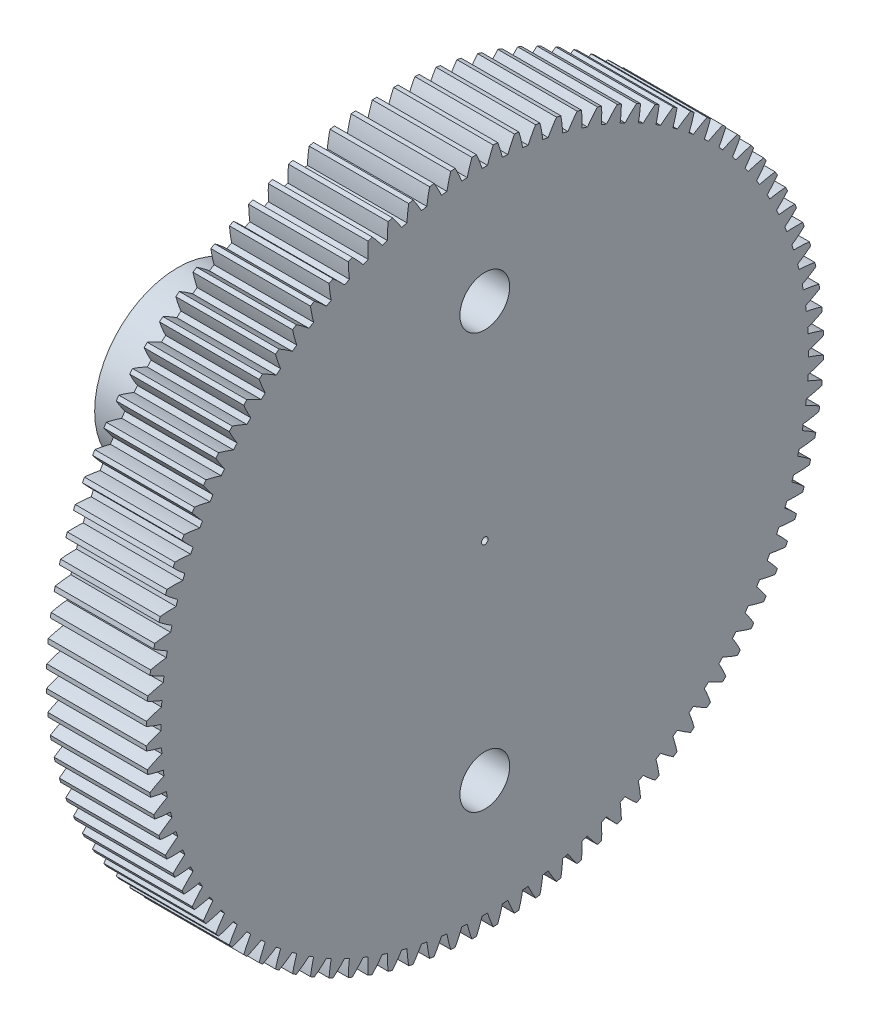
SolidWorks part; units mm, degrees
ref_plane "Plane1" through (0, 0, 0) normal (0, 0, 1) x (1, 0, 0)
ref_plane "Plane2" through (0, 0, 0) normal (0, 1, 0) x (1, 0, 0)
ref_plane "Plane3" through (0, 0, 0) normal (1, 0, 0) x (0, 0, -1)
other "Configuration Table"
sketch "HoldingSke" plane through (0, 0, 0) normal (0, 1, 0) x (1, 0, 0)
  line L0 (0, 0) -> (-0.2171, -1.231)
  line L1 (-15, 0) -> (100, 0) construction
  line L2 (0, 0) -> (-2.1039, 2.3779)
  line L3 (0, 0) -> (-11.863, 4.5341)
  line L4 (0, 0) -> (-1.4996, 8.5048)
  line L5 (0, 0) -> (-46.8476, -17.4728)
  line L6 (0, 0) -> (-9.9476, -6.7116)
  line L7 (-2.1039, 2.3779) -> (8.6586, 51.2059)
  line L8 (-76.2, 54.61) -> (-76.1, 54.61)
  line L9 (-71.009, 38.7566) -> (-53.1078, 45.2721)
  line L10 (-76.2, 71.12) -> (104.1128, 71.12)
  line L11 (0, 0) -> (-12, 0)
  line L12 (-76.2, 101.6) -> (-76.17, 101.6)
  line L13 (24.9733, 27.94) -> (52.9518, 28.4284)
  line L14 (24.9733, 27.94) -> (24.9743, 27.94)
  line L15 (24.9733, 27.94) -> (100.4006, 29.5858)
  line L16 (-63.627, -0.8) -> (-12.827, -0.8)
  circle A0 centre (0, 0) radius 0.4
  circle A1 centre (0, 0) radius 10
  circle A2 centre (0, 0) radius 10
  circle A3 centre (0, 0) radius 0.4
  dimension "Num_teeth" = 100
  dimension "Pitch_radius" = 180.3128
  dimension "Width" = 12
  dimension "Thickness" = 12
sketch "BasProSke" plane through (0, 0, 0) normal (0, 1, 0) x (1, 0, 0)
  line L0 (-10, 0) -> (60, 0) construction
  line L1 (0, 0) -> (0, 40.8)
  line L2 (0, 0) -> (12, 0)
  line L3 (12, 0) -> (12, 40.8)
  line L4 (12, 40.8) -> (0, 40.8)
  dimension "Thickness" = 12
  dimension "Diameter" = 81.6
revolve "Base-Revolve" add sketch "BasProSke" angle 360 about L0
sketch "TooCutSke" plane through (0, 0, 0) normal (1, 0, 0) x (0, 0, -1)
  line L1 (0, 0) -> (0, 107) construction
  line L2 (0, 0) -> (-0.6808, 39.9942) construction
  line L3 (0, 0) -> (-2.5126, 79.9522) construction
  line L4 (-0.6808, 39.9942) -> (-1.2563, 39.9761) construction
  arc A0 (0.331, 38.9976) -> (-0.331, 38.9976) centre (0, 0) ccw
  arc A1 (1.0251, 40.8125) -> (-1.0251, 40.8125) centre (0, 0) ccw
  circle A2 centre (0, 0) radius 40 construction
  circle A3 centre (0, 0) radius 37.5877 construction
  arc A4 (-0.331, 38.9976) -> (-1.0251, 40.8125) centre (-15.5948, 34.2) ccw
  arc A5 (1.0251, 40.8125) -> (0.331, 38.9976) centre (15.5948, 34.2) ccw
extrude "ToothCut" cut sketch "TooCutSke" along normal through all
fillet "Breaks" [suppressed] radius 0.016 tangent propagation no
fillet "RootFillets" [suppressed] radius 0.201
pattern_circular "TeethCuts" count 100 every 3.6 about axis through (-10, 0, 0) along (1, 0, 0) of "ToothCut", "RootFillets", "Breaks"
sketch "HubNeaOneSke" plane through (0, 0, 0) normal (-1, 0, 0) x (0, 0, 1)
  circle A0 centre (0, 0) radius 10
  dimension "Diameter" = 20
sketch "HubNeaBotSke" plane through (0, 0, 0) normal (-1, 0, 0) x (0, 0, 1)
  circle A0 centre (0, 0) radius 10
  dimension "Diameter" = 20
extrude "HubNearBoth" [suppressed] add sketch "HubNeaBotSke" along normal blind 19.0001
ref_plane "FarPln" through (12, 0, 0) normal (1, 0, 0) x (0, 0, -1)
sketch "HubFarSke" plane through (12, 0, 0) normal (1, 0, 0) x (0, 0, -1)
  circle A0 centre (0, 0) radius 10
  dimension "Diameter" = 20
extrude "HubFar" [suppressed] add sketch "HubFarSke" along normal blind 19.0001
sketch "BorSke" plane through (0, 0, 0) normal (1, 0, 0) x (0, 0, -1)
  circle A0 centre (0, 0) radius 0.4
  dimension "Diameter" = 0.8
extrude "Bore" cut sketch "BorSke" along normal mid plane 100.0002
sketch "KeySke" plane through (0, 0, 0) normal (1, 0, 0) x (0, 0, -1)
  line L0 (-0.05, 0) -> (-0.05, 0.5)
  line L1 (-0.05, 0.5) -> (0.05, 0.5)
  line L2 (0.05, 0.5) -> (0.05, 0)
  line L3 (0, 0) -> (0, 34) construction
  line L4 (-0.05, 0) -> (0.05, 0)
  dimension "Width" = 0.1
extrude "Keyway" [suppressed] cut sketch "KeySke" along normal mid plane 100.0002
pattern_circular "Keyway2" [suppressed] count 2 every 90 about axis through (-10, 0, 0) along (1, 0, 0) reverse direction yes
sketch "Sketch1" plane through (12, 0, 0) normal (1, 0, 0) x (0, 0, -1)
  line L0 (0, 42.6862) -> (0, -42.1037) construction
  circle A0 centre (0, 25) radius 3
  circle A1 centre (0, 0) radius 0.4 construction
  circle A2 centre (0, -25) radius 3
  dimension "D1" = 6
  dimension "D2" = 25
  dimension "D3" = 0.0001
  dimension "D4" = 2
extrude "Cut-Extrude1" cut sketch "Sketch1" against normal blind 20
extrude "Boss-Extrude1" add sketch "HubNeaOneSke" along normal blind 25
sketch "Sketch2" plane through (-25, 0, 0) normal (-1, 0, 0) x (0, 0, 1)
  circle A0 centre (3.8479, -0.6356) radius 1
  circle A1 centre (0, 0) radius 10 construction
  circle A2 centre (1.3735, -3.6501) radius 1
  circle A3 centre (-2.4743, -3.0146) radius 1
  circle A4 centre (-3.8479, 0.6356) radius 1
  circle A5 centre (-1.3735, 3.6501) radius 1
  circle A6 centre (2.4743, 3.0146) radius 1
  point P16 (0, 0)
  dimension "D1" = 3.9
  dimension "D2" = 6
extrude "Cut-Extrude2" cut sketch "Sketch2" against normal blind 10
equation "' \"Module@HoldingSke\" = 6.35"
equation "' \"Num_teeth@HoldingSke\" = 12"
equation "' \"Ap@HoldingSke\" =  20"
equation "' \"Ap@HoldingSke\" = 20"
equation "' \"Width@HoldingSke\" = 0.5 * 25.4"
equation "' \"Hub_dia@HoldingSke\"= 1 * 25.4"
equation "' \"Hub_dia@HoldingSke\" = 1 * 25.4"
equation "' \"Overall_len@HoldingSke\" = 1.0 * 25.4"
equation "' \"Bore@HoldingSke\" = 0.75 * 25.4"
equation "' \"T_dim@HoldingSke\" = 0.1 * 25.4"
equation "' \"Width@KeySke\" = 0.25 * 25.4"
equation "' \"Show_teeth@HoldingSke\" = 13"
equation "' \"Backlash@HoldingSke\" = 0.009 * 25.4"
equation "' \"Addendum_fac@HoldingSke\" = 1.0"
equation "' \"Dedendum_fac@HoldingSke\" = 1.25"
equation "' \"Dedendum_add@HoldingSke\" = 0.00005 * 25.4"
equation "' \"Clearance_fac@HoldingSke\" = 0.25"
equation "\"Pitch@HoldingSke\" = 1 / \"Module@HoldingSke\""
equation "\"Overcut_dia@TooCutSke\" = (\"Num_teeth@HoldingSke\" + 2 * \"Addendum_fac@HoldingSke\") / \"Pitch@HoldingSke\" + 0.002 * 25.4"
equation "\"Pitch_dia@TooCutSke\" = \"Num_teeth@HoldingSke\" / \"Pitch@HoldingSke\""
equation "\"Base_dia@TooCutSke\" = \"Num_teeth@HoldingSke\" / \"Pitch@HoldingSke\" * cos((\"Ap@HoldingSke\"  * 3.14159265 / 180))"
equation "\"Root_dia@TooCutSke\" = (\"Num_teeth@HoldingSke\" + 2) / \"Pitch@HoldingSke\" - 2 * (\"Addendum_fac@HoldingSke\" + \"Dedendum_fac@HoldingSke\") / \"Pitch@HoldingSke\" - \"Dedendum_add@HoldingSke\" * 2"
equation "\"Half_ang@TooCutSke\" = 180 / \"Num_teeth@HoldingSke\""
equation "\"Half_CT@TooCutSke\" = \"Num_teeth@HoldingSke\" / \"Pitch@HoldingSke\" * sin((3.14159265 / 2 / \"Num_teeth@HoldingSke\")) / 2 - 7 * \"Backlash@HoldingSke\" / 4"
equation "\"Flank_rad@TooCutSke\" = \"Num_teeth@HoldingSke\" / \"Pitch@HoldingSke\" / 5"
equation "\"Radius@RootFillets\" = \"Clearance_fac@HoldingSke\" / \"Pitch@HoldingSke\" + \"Dedendum_add@HoldingSke\""
equation "\"Break_rad@Breaks\" = 0.02 / \"Pitch@HoldingSke\""
equation "\"Thickness@HoldingSke\" = \"Width@HoldingSke\""
equation "\"OAL@HoldingSke\" = \"Thickness@HoldingSke\""
equation "\"MHD@HoldingSke\" = (\"Num_teeth@HoldingSke\" + 2) / \"Pitch@HoldingSke\" - 2 * (\"Addendum_fac@HoldingSke\" + \"Dedendum_fac@HoldingSke\")  / \"Pitch@HoldingSke\" - \"Dedendum_add@HoldingSke\" * 2"
equation "\"MBD@HoldingSke\" = (\"Num_teeth@HoldingSke\" + 2) / \"Pitch@HoldingSke\" - 2 * (\"Addendum_fac@HoldingSke\" + \"Dedendum_fac@HoldingSke\")  / \"Pitch@HoldingSke\" - \"Dedendum_add@HoldingSke\" * 2 - 0.002 * 25.4"
equation "\"MHD@HoldingSke\" = ((sgn( \"MHD@HoldingSke\" - \"Hub_dia@HoldingSke\" )-1)*( \"MHD@HoldingSke\" - \"Hub_dia@HoldingSke\" ))/-2+ \"Hub_dia@HoldingSke\""
equation "\"MBD@HoldingSke\" = ((sgn( \"MBD@HoldingSke\" - \"Bore@HoldingSke\" )-1)*( \"MBD@HoldingSke\" - \"Bore@HoldingSke\" ))/-2+ \"Bore@HoldingSke\""
equation "\"OAL@HoldingSke\" = ((sgn( \"OAL@HoldingSke\" - \"Overall_len@HoldingSke\" )+1)*( \"OAL@HoldingSke\" - \"Overall_len@HoldingSke\" ))/2 + \"Overall_len@HoldingSke\" + 0.000002 * 25.4"
equation "\"Num_teeth@TeethCuts\" = int( \"Show_teeth@HoldingSke\" ) + 1"
equation "\"Num_teeth@TeethCuts\" = ((sgn( \"Num_teeth@TeethCuts\" - \"Num_teeth@HoldingSke\" )-1)*( \"Num_teeth@TeethCuts\" - \"Num_teeth@HoldingSke\" ))/-2+ \"Num_teeth@HoldingSke\""
equation "\"Num_teeth@TeethCuts\" = ((sgn( \"Num_teeth@TeethCuts\" - 2.0)+1)*( \"Num_teeth@TeethCuts\" - 2.0))/2 +2.0"
equation "\"Angle@TeethCuts\" = 360.0 / \"Num_teeth@HoldingSke\""
equation "\"Diameter@BasProSke\" = (\"Num_teeth@HoldingSke\" + 2 * \"Addendum_fac@HoldingSke\") / \"Pitch@HoldingSke\""
equation "\"Thickness@BasProSke\"  = \"Thickness@HoldingSke\""
equation "' \"Fillet_rad@BasProSke\" =  \"Thickness@HoldingSke\" * 0.05"
equation "' \"Fillet_rad@BasProSke\" = \"Thickness@HoldingSke\" * 0.05"
equation "\"MHD@HoldingSke\" = ((sgn( \"MHD@HoldingSke\" - \"Root_dia@TooCutSke\" )-1)*( \"MHD@HoldingSke\" - \"Root_dia@TooCutSke\" ))/-2+ \"Root_dia@TooCutSke\""
equation "\"Diameter@HubNeaOneSke\" = \"MHD@HoldingSke\""
equation "\"Diameter@HubNeaBotSke\" = \"MHD@HoldingSke\""
equation "\"Length@HubNearBoth\" = ( \"OAL@HoldingSke\" - \"Thickness@BasProSke\" ) / 2.0"
equation "\"Thickness@FarPln\" = \"Thickness@BasProSke\""
equation "\"Diameter@HubFarSke\" = \"MHD@HoldingSke\""
equation "\"Length@HubFar\" = ( \"OAL@HoldingSke\" - \"Thickness@BasProSke\" ) / 2.0"
equation "\"Diameter@BorSke\" = \"MBD@HoldingSke\""
equation "\"D1@Bore\" = \"OAL@HoldingSke\" * 2.0"
equation "\"D1@Keyway\" = \"OAL@HoldingSke\" * 2.0"
equation "\"Offset@KeySke\" = \"T_dim@HoldingSke\" + \"MBD@HoldingSke\" / 2.0"
